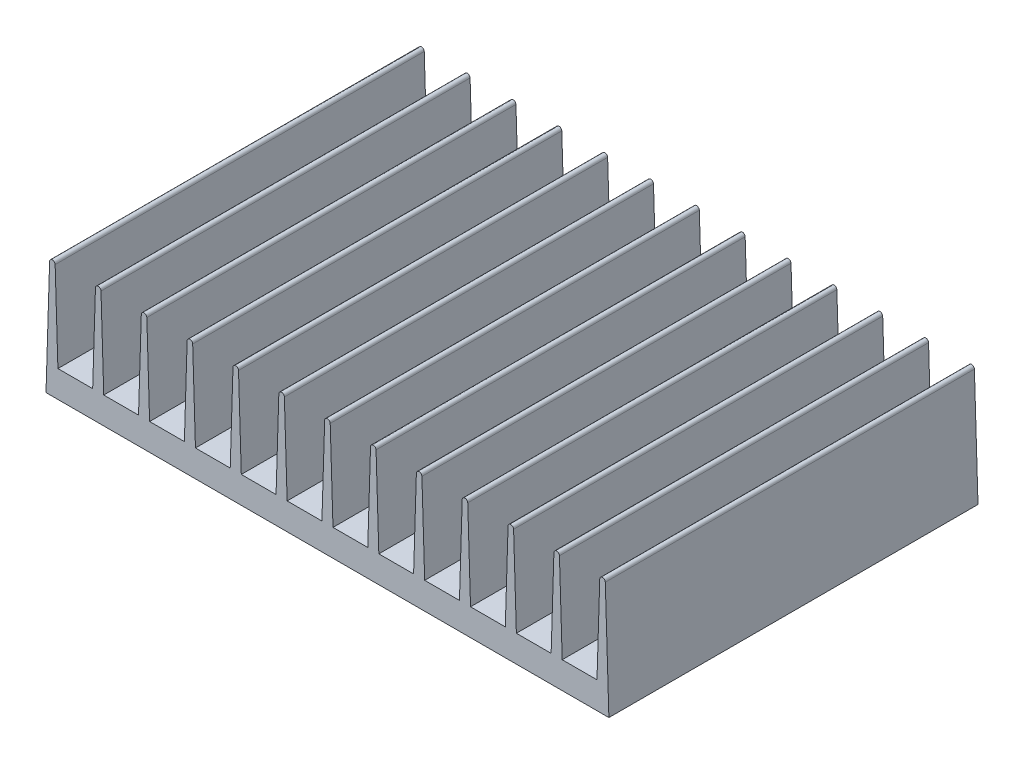
SolidWorks part; units mm, degrees
material "2024-T4"
ref_plane "Front Plane" through (0, 0, 0) normal (0, 0, 1) x (1, 0, 0)
ref_plane "Top Plane" through (0, 0, 0) normal (0, 1, 0) x (1, 0, 0)
ref_plane "Right Plane" through (0, 0, 0) normal (1, 0, 0) x (0, 0, -1)
sketch "Sketch1" plane through (0, 0, 0) normal (0, 0, 1) x (1, 0, 0)
  line L0 (0, 55.0402) -> (0, -45.3994) construction
  line L1 (-61, 0) -> (61, 0)
  line L2 (-61, 0) -> (-60.2189, 25.0187)
  line L3 (-59.6189, -2.7601) -> (-59.6189, 34.7596) construction
  line L4 (-59.0189, 25.0187) -> (-58.4189, 5.8)
  line L5 (-50.8824, 5.8) -> (-50.2824, 25.0187)
  line L6 (-58.4189, 5.8) -> (-50.8824, 5.8)
  line L7 (-49.0824, 25.0187) -> (-48.4824, 5.8)
  line L8 (-40.946, 5.8) -> (-40.346, 25.0187)
  line L9 (-39.146, 25.0187) -> (-38.546, 5.8)
  line L10 (-31.0095, 5.8) -> (-30.4095, 25.0187)
  line L11 (-29.2095, 25.0187) -> (-28.6095, 5.8)
  line L12 (-21.073, 5.8) -> (-20.473, 25.0187)
  line L13 (-19.273, 25.0187) -> (-18.673, 5.8)
  line L14 (-11.1365, 5.8) -> (-10.5365, 25.0187)
  line L15 (-9.3365, 25.0187) -> (-8.7365, 5.8)
  line L16 (-1.2, 5.8) -> (-0.6, 25.0187)
  line L17 (0.6, 25.0187) -> (1.2, 5.8)
  line L18 (8.7365, 5.8) -> (9.3365, 25.0187)
  line L19 (10.5365, 25.0187) -> (11.1365, 5.8)
  line L20 (18.673, 5.8) -> (19.273, 25.0187)
  line L21 (20.473, 25.0187) -> (21.073, 5.8)
  line L22 (28.6095, 5.8) -> (29.2095, 25.0187)
  line L23 (30.4095, 25.0187) -> (31.0095, 5.8)
  line L24 (38.546, 5.8) -> (39.146, 25.0187)
  line L25 (40.346, 25.0187) -> (40.946, 5.8)
  line L26 (48.4824, 5.8) -> (49.0824, 25.0187)
  line L27 (50.2824, 25.0187) -> (50.8824, 5.8)
  line L28 (58.4189, 5.8) -> (59.0189, 25.0187)
  line L29 (60.2189, 25.0187) -> (61, 0)
  line L30 (-48.4824, 5.8) -> (-40.946, 5.8)
  line L31 (-38.546, 5.8) -> (-31.0095, 5.8)
  line L32 (-28.6095, 5.8) -> (-21.073, 5.8)
  line L33 (-18.673, 5.8) -> (-11.1365, 5.8)
  line L34 (-8.7365, 5.8) -> (-1.2, 5.8)
  line L35 (1.2, 5.8) -> (8.7365, 5.8)
  line L36 (11.1365, 5.8) -> (18.673, 5.8)
  line L37 (21.073, 5.8) -> (28.6095, 5.8)
  line L38 (31.0095, 5.8) -> (38.546, 5.8)
  line L39 (40.946, 5.8) -> (48.4824, 5.8)
  line L40 (50.8824, 5.8) -> (58.4189, 5.8)
  line L41 (-40.946, 5.8) -> (-40.8824, 5.8) construction
  line L42 (-41.127, 0) -> (-40.946, 5.8) construction
  line L43 (-31.1905, 0) -> (-31.0095, 5.8) construction
  line L44 (-31.0095, 5.8) -> (-30.8824, 5.8) construction
  line L45 (-21.073, 5.8) -> (-20.8824, 5.8) construction
  line L46 (-21.254, 0) -> (-21.073, 5.8) construction
  line L47 (-11.1365, 5.8) -> (-10.8824, 5.8) construction
  line L48 (-11.3176, 0) -> (-11.1365, 5.8) construction
  line L49 (-1.2, 5.8) -> (-0.8824, 5.8) construction
  line L50 (-1.3811, 0) -> (-1.2, 5.8) construction
  line L51 (8.7365, 5.8) -> (9.1176, 5.8) construction
  line L52 (8.5554, 0) -> (8.7365, 5.8) construction
  line L53 (18.673, 5.8) -> (19.1176, 5.8) construction
  line L54 (18.4919, 0) -> (18.673, 5.8) construction
  line L55 (28.6095, 5.8) -> (29.1176, 5.8) construction
  line L56 (28.4284, 0) -> (28.6095, 5.8) construction
  line L57 (38.546, 5.8) -> (39.1176, 5.8) construction
  line L58 (38.3649, 0) -> (38.546, 5.8) construction
  line L59 (48.4824, 5.8) -> (49.1176, 5.8) construction
  line L60 (48.3014, 0) -> (48.4824, 5.8) construction
  line L61 (58.4189, 5.8) -> (59.1176, 5.8) construction
  line L62 (58.2379, 0) -> (58.4189, 5.8) construction
  line L63 (-51.0635, 0) -> (-50.8824, 5.8) construction
  arc A0 (-60.2189, 25.0187) -> (-59.0189, 25.0187) centre (-59.6189, 25) cw
  arc A1 (-50.2824, 25.0187) -> (-49.0824, 25.0187) centre (-49.6824, 25) cw
  arc A2 (-40.346, 25.0187) -> (-39.146, 25.0187) centre (-39.746, 25) cw
  arc A3 (-30.4095, 25.0187) -> (-29.2095, 25.0187) centre (-29.8095, 25) cw
  arc A4 (-20.473, 25.0187) -> (-19.273, 25.0187) centre (-19.873, 25) cw
  arc A5 (-10.5365, 25.0187) -> (-9.3365, 25.0187) centre (-9.9365, 25) cw
  arc A6 (-0.6, 25.0187) -> (0.6, 25.0187) centre (0, 25) cw
  arc A7 (9.3365, 25.0187) -> (10.5365, 25.0187) centre (9.9365, 25) cw
  arc A8 (19.273, 25.0187) -> (20.473, 25.0187) centre (19.873, 25) cw
  arc A9 (29.2095, 25.0187) -> (30.4095, 25.0187) centre (29.8095, 25) cw
  arc A10 (39.146, 25.0187) -> (40.346, 25.0187) centre (39.746, 25) cw
  arc A11 (49.0824, 25.0187) -> (50.2824, 25.0187) centre (49.6824, 25) cw
  arc A12 (59.0189, 25.0187) -> (60.2189, 25.0187) centre (59.6189, 25) cw
  point P5 (0, 0)
  point P12 (-60.8189, 5.8)
  point P20 (-38.5773, 5.8)
  point P74 (-48.5116, 5.8)
  point P79 (-18.759, 5.8)
  point P81 (0, 0)
  point P83 (0, 0)
  point P85 (11.2732, 5.8)
  point P87 (21.1605, 5.8)
  point P89 (31.2297, 5.8)
  point P91 (40.81, 5.8)
  point P93 (50.777, 5.8)
  point P107 (61, 5.8)
  point P108 (-28.5718, 5.8)
  point P109 (41.0179, 5.8)
  point P110 (0, 0)
  point P111 (50.9915, 5.8)
  dimension "D3" = 2.4
  dimension "D1" = 122
  dimension "D2" = 25
  dimension "D4" = 1.2
  dimension "D5" = 12
  dimension "D6" = 13
  dimension "D7" = 5.8
extrude "Boss-Extrude1" add sketch "Sketch1" along normal mid plane 80
